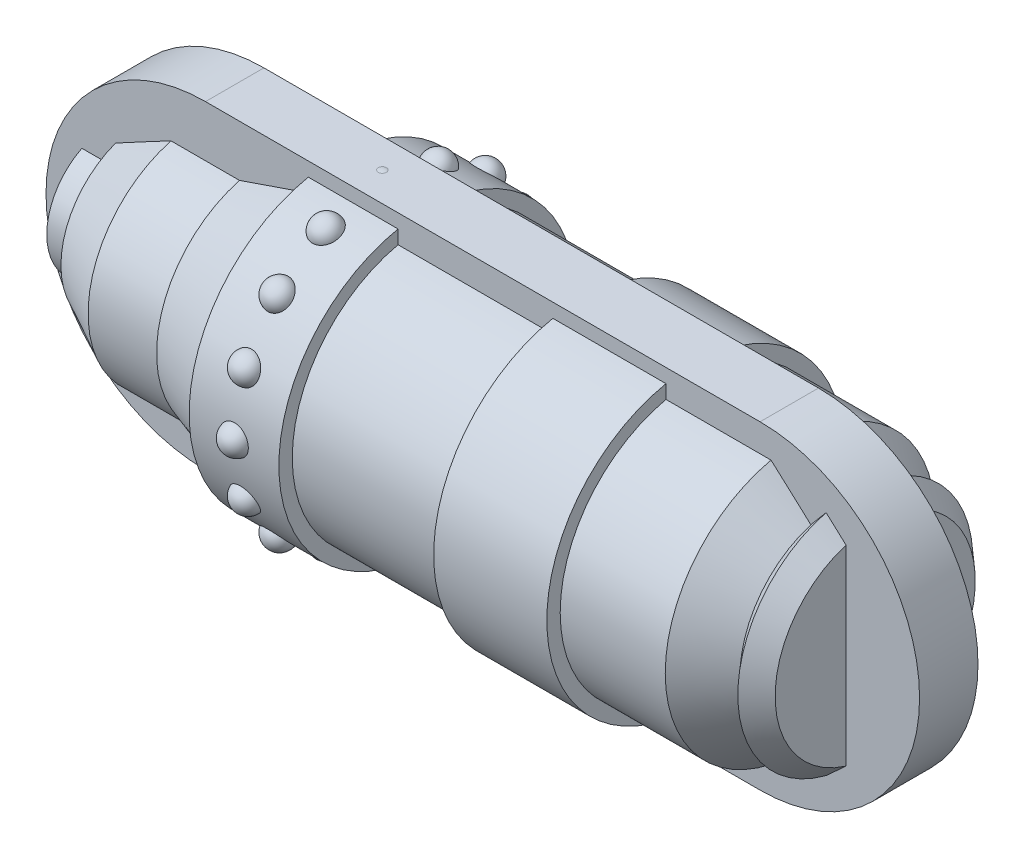
SolidWorks part; units mm, degrees
ref_plane "Front Plane" through (0, 0, 0) normal (0, 0, 1) x (1, 0, 0)
ref_plane "Top Plane" through (0, 0, 0) normal (0, 1, 0) x (1, 0, 0)
ref_plane "Right Plane" through (0, 0, 0) normal (1, 0, 0) x (0, 0, -1)
sketch "Sketch1" plane through (0, 0, 0) normal (0, 0, 1) x (1, 0, 0)
  line L0 (345.0455, 213.0728) -> (428.1044, 213.0728)
  line L1 (369.6596, 227.746) -> (362.1811, 225.2589)
  line L2 (362.1811, 225.2589) -> (354.7359, 225.2589)
  line L3 (354.7359, 225.2589) -> (348.7089, 222.1863)
  line L4 (348.7089, 222.1863) -> (348.7089, 220.0592)
  line L5 (348.7089, 220.0592) -> (345.0455, 220.0592)
  line L6 (345.0455, 220.0592) -> (345.0455, 213.0728)
  line L7 (369.6596, 227.746) -> (369.6596, 229.2015)
  line L8 (194.6218, 229.2015) -> (543.8718, 229.2015) construction
  line L9 (369.6596, 229.2015) -> (379.4138, 229.2015)
  line L10 (379.4138, 229.2015) -> (379.4138, 227.746)
  line L11 (379.4138, 227.746) -> (396.2392, 227.746)
  line L12 (396.2392, 227.746) -> (396.2392, 229.2015)
  line L13 (396.2392, 229.2015) -> (408.5373, 229.2015)
  line L14 (408.5373, 229.2015) -> (408.5373, 227.746)
  line L15 (408.5373, 227.746) -> (419.9548, 227.746)
  line L16 (419.9548, 227.746) -> (424.2771, 223.9508)
  line L17 (424.2771, 223.9508) -> (425.9433, 225.8484)
  line L18 (425.9433, 225.8484) -> (428.1044, 223.9508)
  line L19 (428.1044, 223.9508) -> (428.1044, 213.0728)
revolve "Revolve1" add sketch "Sketch1" angle 360 about L0
sketch "Sketch2" plane through (0, 0, 0) normal (0, 0, 1) x (1, 0, 0)
  line L8 (358.4861, 195.7357) -> (418.7637, 195.7357)
  line L9 (418.7637, 230.4099) -> (358.4861, 230.4099)
  line L10 (358.4861, 195.7357) -> (418.7637, 195.7357)
  line L11 (418.7637, 230.4099) -> (358.4861, 230.4099)
  arc A6 (418.7637, 195.7357) -> (418.7637, 230.4099) centre (418.7637, 213.0728) ccw
  arc A7 (358.4861, 230.4099) -> (358.4861, 195.7357) centre (358.4861, 213.0728) ccw
  arc A8 (418.7637, 195.7357) -> (418.7637, 230.4099) centre (418.7637, 213.0728) ccw
  arc A9 (358.4861, 230.4099) -> (358.4861, 195.7357) centre (358.4861, 213.0728) ccw
  dimension "D1" = 0
extrude "Boss-Extrude1" add sketch "Sketch2" along normal blind 3.175 and the other way blind 3.175
sketch "Sketch3" plane through (0, 0, 0) normal (0, 0, 1) x (1, 0, 0)
  line L0 (379.4138, 228.886) -> (369.6596, 228.886) construction
  line L1 (372.9492, 228.886) -> (376.1242, 228.886)
  arc A0 (376.1242, 228.886) -> (372.9492, 228.886) centre (374.5367, 228.886) ccw
  dimension "D1" = 3.175
revolve "Revolve2" add sketch "Sketch3" angle 360 about L1
pattern_circular "CirPattern1" count 16 over 360 about axis through (345.0455, 213.0728, 0) along (-1, 0, 0) of "Revolve2"
